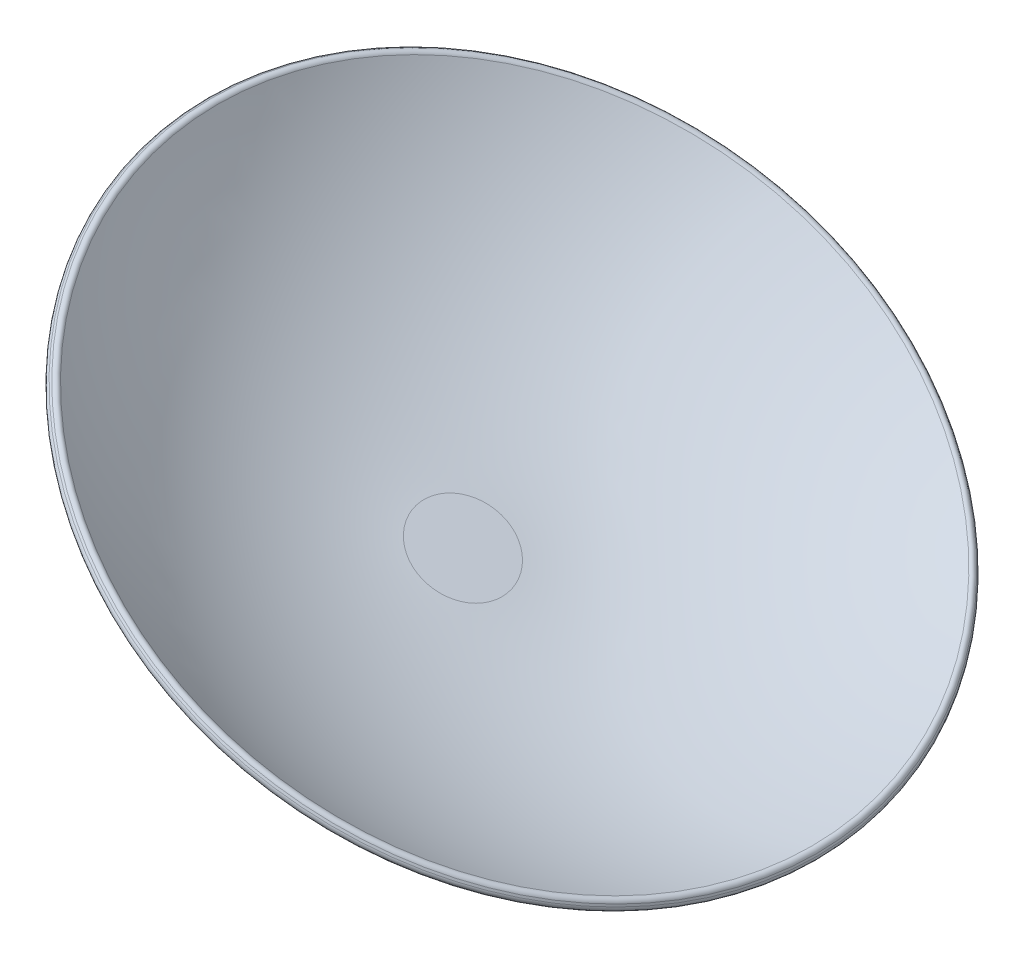
SolidWorks part; units mm, degrees
material "C-Glass Fiber"
ref_plane "Front Plane" through (0, 0, 0) normal (0, 0, 1) x (1, 0, 0)
ref_plane "Top Plane" through (0, 0, 0) normal (0, 1, 0) x (1, 0, 0)
ref_plane "Right Plane" through (0, 0, 0) normal (1, 0, 0) x (0, 0, -1)
sketch "Sketch1" plane through (0, 0, 0) normal (0, 0, 1) x (1, 0, 0)
  line L0 (0, 28.575) -> (0, -28.575)
  arc A0 (0, 28.575) -> (0, -28.575) centre (0, 0) ccw
  dimension "D1" = 57.15
revolve "Revolve1" add sketch "Sketch1" angle 360 about L0
sketch "Sketch3" plane through (0, 0, 0) normal (0, 0, 1) x (1, 0, 0)
  line L0 (0, 0) -> (29.3294, 50.8)
  line L1 (0, 0) -> (28.575, 0) construction
  circle A0 centre (0, 0) radius 28.575 construction
  dimension "D1" = 60
  dimension "D2" = 50.8
sweep "Sweep1" add path "Sketch3" circular profile diameter 12.7 parameters "D3"=12.7
sketch "Sketch48" plane through (0, 0, 0) normal (0, 0, 1) x (1, 0, 0)
  line L0 (29.3294, 50.8) -> (73.2466, 25.2673)
  line L1 (34.8287, 47.625) -> (23.8301, 53.975) construction
  line L2 (35.7126, 61.7793) -> (79.6298, 36.2466)
  line L3 (29.3294, 50.8) -> (35.7126, 61.7793)
  line L4 (433.8743, -31.8862) -> (435.7294, -44.45)
  arc A0 (73.2466, 25.2673) -> (435.7294, -44.45) centre (354.1063, 508.3566) ccw
  arc A1 (79.6298, 36.2466) -> (433.8743, -31.8862) centre (354.1063, 508.3566) ccw
  dimension "D2" = 558.8
  dimension "D1" = 50.8
  dimension "D3" = 406.4
  dimension "D4" = 95.25
  dimension "D5" = 12.7
revolve "Revolve4" add sketch "Sketch48" angle 360 about L3
fillet "Fillet2" radius 5.08 2 edges at (435.7294, -44.45, 0) (433.8743, -31.8862, 0)
ref_axis "Axis1" through (0, 0, 0) along (0.5, 0.866, 0)
